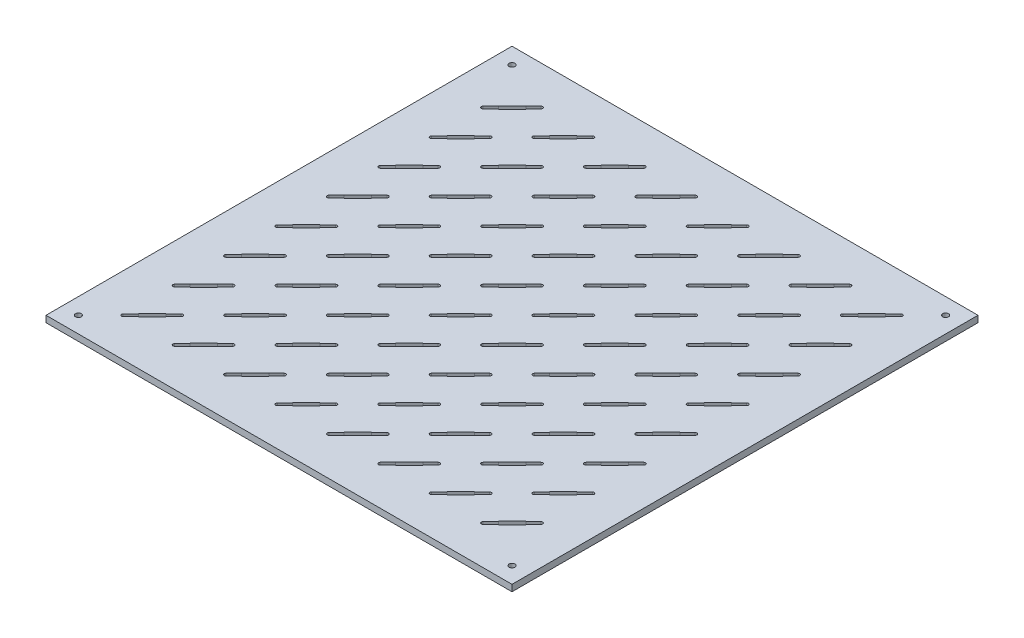
SolidWorks part; units mm, degrees
material "Acrylic (Medium-high impact)"
ref_plane "Front Plane" through (0, 0, 0) normal (0, 0, 1) x (1, 0, 0)
ref_plane "Top Plane" through (0, 0, 0) normal (0, 1, 0) x (1, 0, 0)
ref_plane "Right Plane" through (0, 0, 0) normal (1, 0, 0) x (0, 0, -1)
sketch "Sketch1" plane through (0, 0, 0) normal (0, 1, 0) x (1, 0, 0)
  line L1 (0, 0) -> (431.8, 0)
  line L2 (0, 0) -> (0, 431.8)
  line L3 (0, 431.8) -> (431.8, 431.8)
  line L4 (431.8, 0) -> (431.8, 431.8)
  dimension "D1" = 431.8
  dimension "D2" = 431.8
extrude "Boss-Extrude1" add sketch "Sketch1" along normal blind 6
sketch "Sketch2" plane through (0, 6, 0) normal (0, 1, 0) x (1, 0, 0)
  line L0 (73.025, 25.4) -> (73.025, 73.025) construction
  line L1 (25.4, 25.4) -> (73.025, 25.4) construction
  line L2 (25.4, 25.4) -> (25.4, 73.025) construction
  line L3 (25.4, 73.025) -> (73.025, 73.025) construction
  line L4 (73.025, 25.4) -> (73.025, 73.025) construction
  line L5 (73.025, 25.4) -> (120.65, 25.4) construction
  line L6 (120.65, 25.4) -> (120.65, 73.025) construction
  line L7 (73.025, 73.025) -> (120.65, 73.025) construction
  line L8 (120.65, 25.4) -> (120.65, 73.025) construction
  line L9 (120.65, 25.4) -> (168.275, 25.4) construction
  line L10 (168.275, 25.4) -> (168.275, 73.025) construction
  line L11 (120.65, 73.025) -> (168.275, 73.025) construction
  line L12 (168.275, 25.4) -> (168.275, 73.025) construction
  line L13 (168.275, 25.4) -> (215.9, 25.4) construction
  line L14 (215.9, 25.4) -> (215.9, 73.025) construction
  line L15 (168.275, 73.025) -> (215.9, 73.025) construction
  line L16 (215.9, 25.4) -> (215.9, 73.025) construction
  line L17 (215.9, 25.4) -> (263.525, 25.4) construction
  line L18 (263.525, 25.4) -> (263.525, 73.025) construction
  line L19 (215.9, 73.025) -> (263.525, 73.025) construction
  line L20 (263.525, 25.4) -> (263.525, 73.025) construction
  line L21 (263.525, 25.4) -> (311.15, 25.4) construction
  line L22 (311.15, 25.4) -> (311.15, 73.025) construction
  line L23 (263.525, 73.025) -> (311.15, 73.025) construction
  line L24 (311.15, 25.4) -> (311.15, 73.025) construction
  line L25 (311.15, 25.4) -> (358.775, 25.4) construction
  line L26 (358.775, 25.4) -> (358.775, 73.025) construction
  line L27 (311.15, 73.025) -> (358.775, 73.025) construction
  line L28 (358.775, 25.4) -> (358.775, 73.025) construction
  line L29 (358.775, 25.4) -> (406.4, 25.4) construction
  line L30 (406.4, 25.4) -> (406.4, 73.025) construction
  line L31 (358.775, 73.025) -> (406.4, 73.025) construction
  line L32 (73.025, 73.025) -> (73.025, 120.65) construction
  line L33 (73.025, 73.025) -> (120.65, 73.025) construction
  line L34 (120.65, 73.025) -> (120.65, 120.65) construction
  line L35 (73.025, 120.65) -> (120.65, 120.65) construction
  line L36 (120.65, 73.025) -> (120.65, 120.65) construction
  line L37 (120.65, 73.025) -> (168.275, 73.025) construction
  line L38 (168.275, 73.025) -> (168.275, 120.65) construction
  line L39 (120.65, 120.65) -> (168.275, 120.65) construction
  line L40 (168.275, 73.025) -> (168.275, 120.65) construction
  line L41 (168.275, 73.025) -> (215.9, 73.025) construction
  line L42 (215.9, 73.025) -> (215.9, 120.65) construction
  line L43 (168.275, 120.65) -> (215.9, 120.65) construction
  line L44 (215.9, 73.025) -> (215.9, 120.65) construction
  line L45 (215.9, 73.025) -> (263.525, 73.025) construction
  line L46 (263.525, 73.025) -> (263.525, 120.65) construction
  line L47 (215.9, 120.65) -> (263.525, 120.65) construction
  line L48 (263.525, 73.025) -> (263.525, 120.65) construction
  line L49 (263.525, 73.025) -> (311.15, 73.025) construction
  line L50 (311.15, 73.025) -> (311.15, 120.65) construction
  line L51 (263.525, 120.65) -> (311.15, 120.65) construction
  line L52 (311.15, 73.025) -> (311.15, 120.65) construction
  line L53 (311.15, 73.025) -> (358.775, 73.025) construction
  line L54 (358.775, 73.025) -> (358.775, 120.65) construction
  line L55 (311.15, 120.65) -> (358.775, 120.65) construction
  line L56 (358.775, 73.025) -> (358.775, 120.65) construction
  line L57 (358.775, 73.025) -> (406.4, 73.025) construction
  line L58 (406.4, 73.025) -> (406.4, 120.65) construction
  line L59 (358.775, 120.65) -> (406.4, 120.65) construction
  line L60 (73.025, 120.65) -> (73.025, 168.275) construction
  line L61 (73.025, 120.65) -> (120.65, 120.65) construction
  line L62 (120.65, 120.65) -> (120.65, 168.275) construction
  line L63 (73.025, 168.275) -> (120.65, 168.275) construction
  line L64 (120.65, 120.65) -> (120.65, 168.275) construction
  line L65 (120.65, 120.65) -> (168.275, 120.65) construction
  line L66 (168.275, 120.65) -> (168.275, 168.275) construction
  line L67 (120.65, 168.275) -> (168.275, 168.275) construction
  line L68 (168.275, 120.65) -> (168.275, 168.275) construction
  line L69 (168.275, 120.65) -> (215.9, 120.65) construction
  line L70 (215.9, 120.65) -> (215.9, 168.275) construction
  line L71 (168.275, 168.275) -> (215.9, 168.275) construction
  line L72 (215.9, 120.65) -> (215.9, 168.275) construction
  line L73 (215.9, 120.65) -> (263.525, 120.65) construction
  line L74 (263.525, 120.65) -> (263.525, 168.275) construction
  line L75 (215.9, 168.275) -> (263.525, 168.275) construction
  line L76 (263.525, 120.65) -> (263.525, 168.275) construction
  line L77 (263.525, 120.65) -> (311.15, 120.65) construction
  line L78 (311.15, 120.65) -> (311.15, 168.275) construction
  line L79 (263.525, 168.275) -> (311.15, 168.275) construction
  line L80 (311.15, 120.65) -> (311.15, 168.275) construction
  line L81 (311.15, 120.65) -> (358.775, 120.65) construction
  line L82 (358.775, 120.65) -> (358.775, 168.275) construction
  line L83 (311.15, 168.275) -> (358.775, 168.275) construction
  line L84 (358.775, 120.65) -> (358.775, 168.275) construction
  line L85 (358.775, 120.65) -> (406.4, 120.65) construction
  line L86 (406.4, 120.65) -> (406.4, 168.275) construction
  line L87 (358.775, 168.275) -> (406.4, 168.275) construction
  line L88 (73.025, 168.275) -> (73.025, 215.9) construction
  line L89 (73.025, 168.275) -> (120.65, 168.275) construction
  line L90 (120.65, 168.275) -> (120.65, 215.9) construction
  line L91 (73.025, 215.9) -> (120.65, 215.9) construction
  line L92 (120.65, 168.275) -> (120.65, 215.9) construction
  line L93 (120.65, 168.275) -> (168.275, 168.275) construction
  line L94 (168.275, 168.275) -> (168.275, 215.9) construction
  line L95 (120.65, 215.9) -> (168.275, 215.9) construction
  line L96 (168.275, 168.275) -> (168.275, 215.9) construction
  line L97 (168.275, 168.275) -> (215.9, 168.275) construction
  line L98 (215.9, 168.275) -> (215.9, 215.9) construction
  line L99 (168.275, 215.9) -> (215.9, 215.9) construction
  line L100 (215.9, 168.275) -> (215.9, 215.9) construction
  line L101 (215.9, 168.275) -> (263.525, 168.275) construction
  line L102 (263.525, 168.275) -> (263.525, 215.9) construction
  line L103 (215.9, 215.9) -> (263.525, 215.9) construction
  line L104 (263.525, 168.275) -> (263.525, 215.9) construction
  line L105 (263.525, 168.275) -> (311.15, 168.275) construction
  line L106 (311.15, 168.275) -> (311.15, 215.9) construction
  line L107 (263.525, 215.9) -> (311.15, 215.9) construction
  line L108 (311.15, 168.275) -> (311.15, 215.9) construction
  line L109 (311.15, 168.275) -> (358.775, 168.275) construction
  line L110 (358.775, 168.275) -> (358.775, 215.9) construction
  line L111 (311.15, 215.9) -> (358.775, 215.9) construction
  line L112 (358.775, 168.275) -> (358.775, 215.9) construction
  line L113 (358.775, 168.275) -> (406.4, 168.275) construction
  line L114 (406.4, 168.275) -> (406.4, 215.9) construction
  line L115 (358.775, 215.9) -> (406.4, 215.9) construction
  line L116 (73.025, 215.9) -> (73.025, 263.525) construction
  line L117 (73.025, 215.9) -> (120.65, 215.9) construction
  line L118 (120.65, 215.9) -> (120.65, 263.525) construction
  line L119 (73.025, 263.525) -> (120.65, 263.525) construction
  line L120 (120.65, 215.9) -> (120.65, 263.525) construction
  line L121 (120.65, 215.9) -> (168.275, 215.9) construction
  line L122 (168.275, 215.9) -> (168.275, 263.525) construction
  line L123 (120.65, 263.525) -> (168.275, 263.525) construction
  line L124 (168.275, 215.9) -> (168.275, 263.525) construction
  line L125 (168.275, 215.9) -> (215.9, 215.9) construction
  line L126 (215.9, 215.9) -> (215.9, 263.525) construction
  line L127 (168.275, 263.525) -> (215.9, 263.525) construction
  line L128 (215.9, 215.9) -> (215.9, 263.525) construction
  line L129 (215.9, 215.9) -> (263.525, 215.9) construction
  line L130 (263.525, 215.9) -> (263.525, 263.525) construction
  line L131 (215.9, 263.525) -> (263.525, 263.525) construction
  line L132 (263.525, 215.9) -> (263.525, 263.525) construction
  line L133 (263.525, 215.9) -> (311.15, 215.9) construction
  line L134 (311.15, 215.9) -> (311.15, 263.525) construction
  line L135 (263.525, 263.525) -> (311.15, 263.525) construction
  line L136 (311.15, 215.9) -> (311.15, 263.525) construction
  line L137 (311.15, 215.9) -> (358.775, 215.9) construction
  line L138 (358.775, 215.9) -> (358.775, 263.525) construction
  line L139 (311.15, 263.525) -> (358.775, 263.525) construction
  line L140 (358.775, 215.9) -> (358.775, 263.525) construction
  line L141 (358.775, 215.9) -> (406.4, 215.9) construction
  line L142 (406.4, 215.9) -> (406.4, 263.525) construction
  line L143 (358.775, 263.525) -> (406.4, 263.525) construction
  line L144 (73.025, 263.525) -> (73.025, 311.15) construction
  line L145 (73.025, 263.525) -> (120.65, 263.525) construction
  line L146 (120.65, 263.525) -> (120.65, 311.15) construction
  line L147 (73.025, 311.15) -> (120.65, 311.15) construction
  line L148 (120.65, 263.525) -> (120.65, 311.15) construction
  line L149 (120.65, 263.525) -> (168.275, 263.525) construction
  line L150 (168.275, 263.525) -> (168.275, 311.15) construction
  line L151 (120.65, 311.15) -> (168.275, 311.15) construction
  line L152 (168.275, 263.525) -> (168.275, 311.15) construction
  line L153 (168.275, 263.525) -> (215.9, 263.525) construction
  line L154 (215.9, 263.525) -> (215.9, 311.15) construction
  line L155 (168.275, 311.15) -> (215.9, 311.15) construction
  line L156 (215.9, 263.525) -> (215.9, 311.15) construction
  line L157 (215.9, 263.525) -> (263.525, 263.525) construction
  line L158 (263.525, 263.525) -> (263.525, 311.15) construction
  line L159 (215.9, 311.15) -> (263.525, 311.15) construction
  line L160 (263.525, 263.525) -> (263.525, 311.15) construction
  line L161 (263.525, 263.525) -> (311.15, 263.525) construction
  line L162 (311.15, 263.525) -> (311.15, 311.15) construction
  line L163 (263.525, 311.15) -> (311.15, 311.15) construction
  line L164 (311.15, 263.525) -> (311.15, 311.15) construction
  line L165 (311.15, 263.525) -> (358.775, 263.525) construction
  line L166 (358.775, 263.525) -> (358.775, 311.15) construction
  line L167 (311.15, 311.15) -> (358.775, 311.15) construction
  line L168 (358.775, 263.525) -> (358.775, 311.15) construction
  line L169 (358.775, 263.525) -> (406.4, 263.525) construction
  line L170 (406.4, 263.525) -> (406.4, 311.15) construction
  line L171 (358.775, 311.15) -> (406.4, 311.15) construction
  line L172 (73.025, 311.15) -> (73.025, 358.775) construction
  line L173 (73.025, 311.15) -> (120.65, 311.15) construction
  line L174 (120.65, 311.15) -> (120.65, 358.775) construction
  line L175 (73.025, 358.775) -> (120.65, 358.775) construction
  line L176 (120.65, 311.15) -> (120.65, 358.775) construction
  line L177 (120.65, 311.15) -> (168.275, 311.15) construction
  line L178 (168.275, 311.15) -> (168.275, 358.775) construction
  line L179 (120.65, 358.775) -> (168.275, 358.775) construction
  line L180 (168.275, 311.15) -> (168.275, 358.775) construction
  line L181 (168.275, 311.15) -> (215.9, 311.15) construction
  line L182 (215.9, 311.15) -> (215.9, 358.775) construction
  line L183 (168.275, 358.775) -> (215.9, 358.775) construction
  line L184 (215.9, 311.15) -> (215.9, 358.775) construction
  line L185 (215.9, 311.15) -> (263.525, 311.15) construction
  line L186 (263.525, 311.15) -> (263.525, 358.775) construction
  line L187 (215.9, 358.775) -> (263.525, 358.775) construction
  line L188 (263.525, 311.15) -> (263.525, 358.775) construction
  line L189 (263.525, 311.15) -> (311.15, 311.15) construction
  line L190 (311.15, 311.15) -> (311.15, 358.775) construction
  line L191 (263.525, 358.775) -> (311.15, 358.775) construction
  line L192 (311.15, 311.15) -> (311.15, 358.775) construction
  line L193 (311.15, 311.15) -> (358.775, 311.15) construction
  line L194 (358.775, 311.15) -> (358.775, 358.775) construction
  line L195 (311.15, 358.775) -> (358.775, 358.775) construction
  line L196 (358.775, 311.15) -> (358.775, 358.775) construction
  line L197 (358.775, 311.15) -> (406.4, 311.15) construction
  line L198 (406.4, 311.15) -> (406.4, 358.775) construction
  line L199 (358.775, 358.775) -> (406.4, 358.775) construction
  line L200 (73.025, 358.775) -> (73.025, 406.4) construction
  line L201 (73.025, 358.775) -> (120.65, 358.775) construction
  line L202 (120.65, 358.775) -> (120.65, 406.4) construction
  line L203 (73.025, 406.4) -> (120.65, 406.4) construction
  line L204 (120.65, 358.775) -> (120.65, 406.4) construction
  line L205 (120.65, 358.775) -> (168.275, 358.775) construction
  line L206 (168.275, 358.775) -> (168.275, 406.4) construction
  line L207 (120.65, 406.4) -> (168.275, 406.4) construction
  line L208 (168.275, 358.775) -> (168.275, 406.4) construction
  line L209 (168.275, 358.775) -> (215.9, 358.775) construction
  line L210 (215.9, 358.775) -> (215.9, 406.4) construction
  line L211 (168.275, 406.4) -> (215.9, 406.4) construction
  line L212 (215.9, 358.775) -> (215.9, 406.4) construction
  line L213 (215.9, 358.775) -> (263.525, 358.775) construction
  line L214 (263.525, 358.775) -> (263.525, 406.4) construction
  line L215 (215.9, 406.4) -> (263.525, 406.4) construction
  line L216 (263.525, 358.775) -> (263.525, 406.4) construction
  line L217 (263.525, 358.775) -> (311.15, 358.775) construction
  line L218 (311.15, 358.775) -> (311.15, 406.4) construction
  line L219 (263.525, 406.4) -> (311.15, 406.4) construction
  line L220 (311.15, 358.775) -> (311.15, 406.4) construction
  line L221 (311.15, 358.775) -> (358.775, 358.775) construction
  line L222 (358.775, 358.775) -> (358.775, 406.4) construction
  line L223 (311.15, 406.4) -> (358.775, 406.4) construction
  line L224 (358.775, 358.775) -> (358.775, 406.4) construction
  line L225 (358.775, 358.775) -> (406.4, 358.775) construction
  line L226 (406.4, 358.775) -> (406.4, 406.4) construction
  line L227 (358.775, 406.4) -> (406.4, 406.4) construction
  line L228 (25.4, 73.025) -> (25.4, 120.65) construction
  line L229 (25.4, 73.025) -> (73.025, 73.025) construction
  line L230 (73.025, 73.025) -> (73.025, 120.65) construction
  line L231 (25.4, 120.65) -> (73.025, 120.65) construction
  line L232 (25.4, 120.65) -> (25.4, 168.275) construction
  line L233 (25.4, 120.65) -> (73.025, 120.65) construction
  line L234 (73.025, 120.65) -> (73.025, 168.275) construction
  line L235 (25.4, 168.275) -> (73.025, 168.275) construction
  line L236 (25.4, 168.275) -> (25.4, 215.9) construction
  line L237 (25.4, 168.275) -> (73.025, 168.275) construction
  line L238 (73.025, 168.275) -> (73.025, 215.9) construction
  line L239 (25.4, 215.9) -> (73.025, 215.9) construction
  line L240 (25.4, 215.9) -> (25.4, 263.525) construction
  line L241 (25.4, 215.9) -> (73.025, 215.9) construction
  line L242 (73.025, 215.9) -> (73.025, 263.525) construction
  line L243 (25.4, 263.525) -> (73.025, 263.525) construction
  line L244 (25.4, 263.525) -> (25.4, 311.15) construction
  line L245 (25.4, 263.525) -> (73.025, 263.525) construction
  line L246 (73.025, 263.525) -> (73.025, 311.15) construction
  line L247 (25.4, 311.15) -> (73.025, 311.15) construction
  line L248 (25.4, 311.15) -> (25.4, 358.775) construction
  line L249 (25.4, 311.15) -> (73.025, 311.15) construction
  line L250 (73.025, 311.15) -> (73.025, 358.775) construction
  line L251 (25.4, 358.775) -> (73.025, 358.775) construction
  line L252 (25.4, 358.775) -> (25.4, 406.4) construction
  line L253 (25.4, 358.775) -> (73.025, 358.775) construction
  line L254 (73.025, 358.775) -> (73.025, 406.4) construction
  line L255 (25.4, 406.4) -> (73.025, 406.4) construction
  line L256 (0, 0) -> (431.8, 0) construction
  line L257 (0, 431.8) -> (0, 0) construction
  line L259 (431.8, 431.8) -> (0, 431.8) construction
  line L260 (431.8, 0) -> (431.8, 431.8) construction
  line L261 (73.025, 73.025) -> (25.4, 25.4) construction
  line L266 (41.7253, 43.9704) -> (34.6543, 36.8993)
  line L906 (56.99, 54.1616) -> (56.6983, 54.4532)
  line L922 (56.99, 54.1616) -> (44.2621, 41.4336)
  line L923 (44.2621, 41.4336) -> (43.9704, 41.7253)
  line L924 (54.1616, 56.99) -> (41.4336, 44.2621)
  line L925 (34.6543, 36.8993) -> (36.8993, 34.6543)
  line L926 (36.8993, 34.6543) -> (43.9704, 41.7253)
  line L927 (41.7253, 43.9704) -> (41.4336, 44.2621)
  line L928 (54.4532, 56.6983) -> (61.5243, 63.7694)
  line L929 (61.5243, 63.7694) -> (63.7694, 61.5243)
  line L930 (63.7694, 61.5243) -> (56.6983, 54.4532)
  line L931 (54.4532, 56.6983) -> (54.1616, 56.99)
  line L932 (25.4, 73.025) -> (73.025, 25.4) construction
  line L933 (56.99, 101.7916) -> (56.6983, 102.0832)
  line L934 (63.7694, 109.1543) -> (56.6983, 102.0832)
  line L935 (61.5243, 111.3994) -> (63.7694, 109.1543)
  line L936 (54.4532, 104.3283) -> (61.5243, 111.3994)
  line L937 (54.4532, 104.3283) -> (54.1616, 104.62)
  line L938 (54.1616, 104.62) -> (41.4336, 91.8921)
  line L939 (41.7253, 91.6004) -> (41.4336, 91.8921)
  line L940 (41.7253, 91.6004) -> (34.6543, 84.5293)
  line L941 (34.6543, 84.5293) -> (36.8993, 82.2843)
  line L942 (36.8993, 82.2843) -> (43.9704, 89.3553)
  line L943 (44.2621, 89.0636) -> (43.9704, 89.3553)
  line L944 (56.99, 101.7916) -> (44.2621, 89.0636)
  line L945 (56.99, 149.4216) -> (56.6983, 149.7132)
  line L946 (63.7694, 156.7843) -> (56.6983, 149.7132)
  line L947 (61.5243, 159.0294) -> (63.7694, 156.7843)
  line L948 (54.4532, 151.9583) -> (61.5243, 159.0294)
  line L949 (54.4532, 151.9583) -> (54.1616, 152.25)
  line L950 (54.1616, 152.25) -> (41.4336, 139.5221)
  line L951 (41.7253, 139.2304) -> (41.4336, 139.5221)
  line L952 (41.7253, 139.2304) -> (34.6543, 132.1593)
  line L953 (34.6543, 132.1593) -> (36.8993, 129.9143)
  line L954 (36.8993, 129.9143) -> (43.9704, 136.9853)
  line L955 (44.2621, 136.6936) -> (43.9704, 136.9853)
  line L956 (56.99, 149.4216) -> (44.2621, 136.6936)
  line L957 (56.99, 197.0516) -> (56.6983, 197.3432)
  line L958 (63.7694, 204.4143) -> (56.6983, 197.3432)
  line L959 (61.5243, 206.6594) -> (63.7694, 204.4143)
  line L960 (54.4532, 199.5883) -> (61.5243, 206.6594)
  line L961 (54.4532, 199.5883) -> (54.1616, 199.88)
  line L962 (54.1616, 199.88) -> (41.4336, 187.1521)
  line L963 (41.7253, 186.8604) -> (41.4336, 187.1521)
  line L964 (41.7253, 186.8604) -> (34.6543, 179.7893)
  line L965 (34.6543, 179.7893) -> (36.8993, 177.5443)
  line L966 (36.8993, 177.5443) -> (43.9704, 184.6153)
  line L967 (44.2621, 184.3236) -> (43.9704, 184.6153)
  line L968 (56.99, 197.0516) -> (44.2621, 184.3236)
  line L969 (56.99, 244.6816) -> (56.6983, 244.9732)
  line L970 (63.7694, 252.0443) -> (56.6983, 244.9732)
  line L971 (61.5243, 254.2894) -> (63.7694, 252.0443)
  line L972 (54.4532, 247.2183) -> (61.5243, 254.2894)
  line L973 (54.4532, 247.2183) -> (54.1616, 247.51)
  line L974 (54.1616, 247.51) -> (41.4336, 234.7821)
  line L975 (41.7253, 234.4904) -> (41.4336, 234.7821)
  line L976 (41.7253, 234.4904) -> (34.6543, 227.4193)
  line L977 (34.6543, 227.4193) -> (36.8993, 225.1743)
  line L978 (36.8993, 225.1743) -> (43.9704, 232.2453)
  line L979 (44.2621, 231.9536) -> (43.9704, 232.2453)
  line L980 (56.99, 244.6816) -> (44.2621, 231.9536)
  line L981 (56.99, 292.3116) -> (56.6983, 292.6032)
  line L982 (63.7694, 299.6743) -> (56.6983, 292.6032)
  line L983 (61.5243, 301.9194) -> (63.7694, 299.6743)
  line L984 (54.4532, 294.8483) -> (61.5243, 301.9194)
  line L985 (54.4532, 294.8483) -> (54.1616, 295.14)
  line L986 (54.1616, 295.14) -> (41.4336, 282.4121)
  line L987 (41.7253, 282.1204) -> (41.4336, 282.4121)
  line L988 (41.7253, 282.1204) -> (34.6543, 275.0493)
  line L989 (34.6543, 275.0493) -> (36.8993, 272.8043)
  line L990 (36.8993, 272.8043) -> (43.9704, 279.8753)
  line L991 (44.2621, 279.5836) -> (43.9704, 279.8753)
  line L992 (56.99, 292.3116) -> (44.2621, 279.5836)
  line L993 (56.99, 339.9416) -> (56.6983, 340.2332)
  line L994 (63.7694, 347.3043) -> (56.6983, 340.2332)
  line L995 (61.5243, 349.5494) -> (63.7694, 347.3043)
  line L996 (54.4532, 342.4783) -> (61.5243, 349.5494)
  line L997 (54.4532, 342.4783) -> (54.1616, 342.77)
  line L998 (54.1616, 342.77) -> (41.4336, 330.0421)
  line L999 (41.7253, 329.7504) -> (41.4336, 330.0421)
  line L1000 (41.7253, 329.7504) -> (34.6543, 322.6793)
  line L1001 (34.6543, 322.6793) -> (36.8993, 320.4343)
  line L1002 (36.8993, 320.4343) -> (43.9704, 327.5053)
  line L1003 (44.2621, 327.2136) -> (43.9704, 327.5053)
  line L1004 (56.99, 339.9416) -> (44.2621, 327.2136)
  line L1005 (56.99, 387.5716) -> (56.6983, 387.8632)
  line L1006 (63.7694, 394.9343) -> (56.6983, 387.8632)
  line L1007 (61.5243, 397.1794) -> (63.7694, 394.9343)
  line L1008 (54.4532, 390.1083) -> (61.5243, 397.1794)
  line L1009 (54.4532, 390.1083) -> (54.1616, 390.4)
  line L1010 (54.1616, 390.4) -> (41.4336, 377.6721)
  line L1011 (41.7253, 377.3804) -> (41.4336, 377.6721)
  line L1012 (41.7253, 377.3804) -> (34.6543, 370.3093)
  line L1013 (34.6543, 370.3093) -> (36.8993, 368.0643)
  line L1014 (36.8993, 368.0643) -> (43.9704, 375.1353)
  line L1015 (44.2621, 374.8436) -> (43.9704, 375.1353)
  line L1016 (56.99, 387.5716) -> (44.2621, 374.8436)
  line L1017 (104.62, 101.7916) -> (104.3283, 102.0832)
  line L1018 (111.3994, 109.1543) -> (104.3283, 102.0832)
  line L1019 (109.1543, 111.3994) -> (111.3994, 109.1543)
  line L1020 (102.0832, 104.3283) -> (109.1543, 111.3994)
  line L1021 (102.0832, 104.3283) -> (101.7916, 104.62)
  line L1022 (101.7916, 104.62) -> (89.0636, 91.8921)
  line L1023 (89.3553, 91.6004) -> (89.0636, 91.8921)
  line L1024 (89.3553, 91.6004) -> (82.2843, 84.5293)
  line L1025 (82.2843, 84.5293) -> (84.5293, 82.2843)
  line L1026 (84.5293, 82.2843) -> (91.6004, 89.3553)
  line L1027 (91.8921, 89.0636) -> (91.6004, 89.3553)
  line L1028 (104.62, 101.7916) -> (91.8921, 89.0636)
  line L1029 (104.62, 149.4216) -> (104.3283, 149.7132)
  line L1030 (111.3994, 156.7843) -> (104.3283, 149.7132)
  line L1031 (109.1543, 159.0294) -> (111.3994, 156.7843)
  line L1032 (102.0832, 151.9583) -> (109.1543, 159.0294)
  line L1033 (102.0832, 151.9583) -> (101.7916, 152.25)
  line L1034 (101.7916, 152.25) -> (89.0636, 139.5221)
  line L1035 (89.3553, 139.2304) -> (89.0636, 139.5221)
  line L1036 (89.3553, 139.2304) -> (82.2843, 132.1593)
  line L1037 (82.2843, 132.1593) -> (84.5293, 129.9143)
  line L1038 (84.5293, 129.9143) -> (91.6004, 136.9853)
  line L1039 (91.8921, 136.6936) -> (91.6004, 136.9853)
  line L1040 (104.62, 149.4216) -> (91.8921, 136.6936)
  line L1041 (104.62, 197.0516) -> (104.3283, 197.3432)
  line L1042 (111.3994, 204.4143) -> (104.3283, 197.3432)
  line L1043 (109.1543, 206.6594) -> (111.3994, 204.4143)
  line L1044 (102.0832, 199.5883) -> (109.1543, 206.6594)
  line L1045 (102.0832, 199.5883) -> (101.7916, 199.88)
  line L1046 (101.7916, 199.88) -> (89.0636, 187.1521)
  line L1047 (89.3553, 186.8604) -> (89.0636, 187.1521)
  line L1048 (89.3553, 186.8604) -> (82.2843, 179.7893)
  line L1049 (82.2843, 179.7893) -> (84.5293, 177.5443)
  line L1050 (84.5293, 177.5443) -> (91.6004, 184.6153)
  line L1051 (91.8921, 184.3236) -> (91.6004, 184.6153)
  line L1052 (104.62, 197.0516) -> (91.8921, 184.3236)
  line L1053 (104.62, 244.6816) -> (104.3283, 244.9732)
  line L1054 (111.3994, 252.0443) -> (104.3283, 244.9732)
  line L1055 (109.1543, 254.2894) -> (111.3994, 252.0443)
  line L1056 (102.0832, 247.2183) -> (109.1543, 254.2894)
  line L1057 (102.0832, 247.2183) -> (101.7916, 247.51)
  line L1058 (101.7916, 247.51) -> (89.0636, 234.7821)
  line L1059 (89.3553, 234.4904) -> (89.0636, 234.7821)
  line L1060 (89.3553, 234.4904) -> (82.2843, 227.4193)
  line L1061 (82.2843, 227.4193) -> (84.5293, 225.1743)
  line L1062 (84.5293, 225.1743) -> (91.6004, 232.2453)
  line L1063 (91.8921, 231.9536) -> (91.6004, 232.2453)
  line L1064 (104.62, 244.6816) -> (91.8921, 231.9536)
  line L1065 (104.62, 292.3116) -> (104.3283, 292.6032)
  line L1066 (111.3994, 299.6743) -> (104.3283, 292.6032)
  line L1067 (109.1543, 301.9194) -> (111.3994, 299.6743)
  line L1068 (102.0832, 294.8483) -> (109.1543, 301.9194)
  line L1069 (102.0832, 294.8483) -> (101.7916, 295.14)
  line L1070 (101.7916, 295.14) -> (89.0636, 282.4121)
  line L1071 (89.3553, 282.1204) -> (89.0636, 282.4121)
  line L1072 (89.3553, 282.1204) -> (82.2843, 275.0493)
  line L1073 (82.2843, 275.0493) -> (84.5293, 272.8043)
  line L1074 (84.5293, 272.8043) -> (91.6004, 279.8753)
  line L1075 (91.8921, 279.5836) -> (91.6004, 279.8753)
  line L1076 (104.62, 292.3116) -> (91.8921, 279.5836)
  line L1077 (104.62, 339.9416) -> (104.3283, 340.2332)
  line L1078 (111.3994, 347.3043) -> (104.3283, 340.2332)
  line L1079 (109.1543, 349.5494) -> (111.3994, 347.3043)
  line L1080 (102.0832, 342.4783) -> (109.1543, 349.5494)
  line L1081 (102.0832, 342.4783) -> (101.7916, 342.77)
  line L1082 (101.7916, 342.77) -> (89.0636, 330.0421)
  line L1083 (89.3553, 329.7504) -> (89.0636, 330.0421)
  line L1084 (89.3553, 329.7504) -> (82.2843, 322.6793)
  line L1085 (82.2843, 322.6793) -> (84.5293, 320.4343)
  line L1086 (84.5293, 320.4343) -> (91.6004, 327.5053)
  line L1087 (91.8921, 327.2136) -> (91.6004, 327.5053)
  line L1088 (104.62, 339.9416) -> (91.8921, 327.2136)
  line L1089 (104.62, 387.5716) -> (104.3283, 387.8632)
  line L1090 (111.3994, 394.9343) -> (104.3283, 387.8632)
  line L1091 (109.1543, 397.1794) -> (111.3994, 394.9343)
  line L1092 (102.0832, 390.1083) -> (109.1543, 397.1794)
  line L1093 (102.0832, 390.1083) -> (101.7916, 390.4)
  line L1094 (101.7916, 390.4) -> (89.0636, 377.6721)
  line L1095 (89.3553, 377.3804) -> (89.0636, 377.6721)
  line L1096 (89.3553, 377.3804) -> (82.2843, 370.3093)
  line L1097 (82.2843, 370.3093) -> (84.5293, 368.0643)
  line L1098 (84.5293, 368.0643) -> (91.6004, 375.1353)
  line L1099 (91.8921, 374.8436) -> (91.6004, 375.1353)
  line L1100 (104.62, 387.5716) -> (91.8921, 374.8436)
  line L1101 (152.25, 101.7916) -> (151.9583, 102.0832)
  line L1102 (159.0294, 109.1543) -> (151.9583, 102.0832)
  line L1103 (156.7843, 111.3994) -> (159.0294, 109.1543)
  line L1104 (149.7132, 104.3283) -> (156.7843, 111.3994)
  line L1105 (149.7132, 104.3283) -> (149.4216, 104.62)
  line L1106 (149.4216, 104.62) -> (136.6936, 91.8921)
  line L1107 (136.9853, 91.6004) -> (136.6936, 91.8921)
  line L1108 (136.9853, 91.6004) -> (129.9143, 84.5293)
  line L1109 (129.9143, 84.5293) -> (132.1593, 82.2843)
  line L1110 (132.1593, 82.2843) -> (139.2304, 89.3553)
  line L1111 (139.5221, 89.0636) -> (139.2304, 89.3553)
  line L1112 (152.25, 101.7916) -> (139.5221, 89.0636)
  line L1113 (152.25, 149.4216) -> (151.9583, 149.7132)
  line L1114 (159.0294, 156.7843) -> (151.9583, 149.7132)
  line L1115 (156.7843, 159.0294) -> (159.0294, 156.7843)
  line L1116 (149.7132, 151.9583) -> (156.7843, 159.0294)
  line L1117 (149.7132, 151.9583) -> (149.4216, 152.25)
  line L1118 (149.4216, 152.25) -> (136.6936, 139.5221)
  line L1119 (136.9853, 139.2304) -> (136.6936, 139.5221)
  line L1120 (136.9853, 139.2304) -> (129.9143, 132.1593)
  line L1121 (129.9143, 132.1593) -> (132.1593, 129.9143)
  line L1122 (132.1593, 129.9143) -> (139.2304, 136.9853)
  line L1123 (139.5221, 136.6936) -> (139.2304, 136.9853)
  line L1124 (152.25, 149.4216) -> (139.5221, 136.6936)
  line L1125 (152.25, 197.0516) -> (151.9583, 197.3432)
  line L1126 (159.0294, 204.4143) -> (151.9583, 197.3432)
  line L1127 (156.7843, 206.6594) -> (159.0294, 204.4143)
  line L1128 (149.7132, 199.5883) -> (156.7843, 206.6594)
  line L1129 (149.7132, 199.5883) -> (149.4216, 199.88)
  line L1130 (149.4216, 199.88) -> (136.6936, 187.1521)
  line L1131 (136.9853, 186.8604) -> (136.6936, 187.1521)
  line L1132 (136.9853, 186.8604) -> (129.9143, 179.7893)
  line L1133 (129.9143, 179.7893) -> (132.1593, 177.5443)
  line L1134 (132.1593, 177.5443) -> (139.2304, 184.6153)
  line L1135 (139.5221, 184.3236) -> (139.2304, 184.6153)
  line L1136 (152.25, 197.0516) -> (139.5221, 184.3236)
  line L1137 (152.25, 244.6816) -> (151.9583, 244.9732)
  line L1138 (159.0294, 252.0443) -> (151.9583, 244.9732)
  line L1139 (156.7843, 254.2894) -> (159.0294, 252.0443)
  line L1140 (149.7132, 247.2183) -> (156.7843, 254.2894)
  line L1141 (149.7132, 247.2183) -> (149.4216, 247.51)
  line L1142 (149.4216, 247.51) -> (136.6936, 234.7821)
  line L1143 (136.9853, 234.4904) -> (136.6936, 234.7821)
  line L1144 (136.9853, 234.4904) -> (129.9143, 227.4193)
  line L1145 (129.9143, 227.4193) -> (132.1593, 225.1743)
  line L1146 (132.1593, 225.1743) -> (139.2304, 232.2453)
  line L1147 (139.5221, 231.9536) -> (139.2304, 232.2453)
  line L1148 (152.25, 244.6816) -> (139.5221, 231.9536)
  line L1149 (152.25, 292.3116) -> (151.9583, 292.6032)
  line L1150 (159.0294, 299.6743) -> (151.9583, 292.6032)
  line L1151 (156.7843, 301.9194) -> (159.0294, 299.6743)
  line L1152 (149.7132, 294.8483) -> (156.7843, 301.9194)
  line L1153 (149.7132, 294.8483) -> (149.4216, 295.14)
  line L1154 (149.4216, 295.14) -> (136.6936, 282.4121)
  line L1155 (136.9853, 282.1204) -> (136.6936, 282.4121)
  line L1156 (136.9853, 282.1204) -> (129.9143, 275.0493)
  line L1157 (129.9143, 275.0493) -> (132.1593, 272.8043)
  line L1158 (132.1593, 272.8043) -> (139.2304, 279.8753)
  line L1159 (139.5221, 279.5836) -> (139.2304, 279.8753)
  line L1160 (152.25, 292.3116) -> (139.5221, 279.5836)
  line L1161 (152.25, 339.9416) -> (151.9583, 340.2332)
  line L1162 (159.0294, 347.3043) -> (151.9583, 340.2332)
  line L1163 (156.7843, 349.5494) -> (159.0294, 347.3043)
  line L1164 (149.7132, 342.4783) -> (156.7843, 349.5494)
  line L1165 (149.7132, 342.4783) -> (149.4216, 342.77)
  line L1166 (149.4216, 342.77) -> (136.6936, 330.0421)
  line L1167 (136.9853, 329.7504) -> (136.6936, 330.0421)
  line L1168 (136.9853, 329.7504) -> (129.9143, 322.6793)
  line L1169 (129.9143, 322.6793) -> (132.1593, 320.4343)
  line L1170 (132.1593, 320.4343) -> (139.2304, 327.5053)
  line L1171 (139.5221, 327.2136) -> (139.2304, 327.5053)
  line L1172 (152.25, 339.9416) -> (139.5221, 327.2136)
  line L1173 (152.25, 387.5716) -> (151.9583, 387.8632)
  line L1174 (159.0294, 394.9343) -> (151.9583, 387.8632)
  line L1175 (156.7843, 397.1794) -> (159.0294, 394.9343)
  line L1176 (149.7132, 390.1083) -> (156.7843, 397.1794)
  line L1177 (149.7132, 390.1083) -> (149.4216, 390.4)
  line L1178 (149.4216, 390.4) -> (136.6936, 377.6721)
  line L1179 (136.9853, 377.3804) -> (136.6936, 377.6721)
  line L1180 (136.9853, 377.3804) -> (129.9143, 370.3093)
  line L1181 (129.9143, 370.3093) -> (132.1593, 368.0643)
  line L1182 (132.1593, 368.0643) -> (139.2304, 375.1353)
  line L1183 (139.5221, 374.8436) -> (139.2304, 375.1353)
  line L1184 (152.25, 387.5716) -> (139.5221, 374.8436)
  line L1185 (199.88, 101.7916) -> (199.5883, 102.0832)
  line L1186 (206.6594, 109.1543) -> (199.5883, 102.0832)
  line L1187 (204.4143, 111.3994) -> (206.6594, 109.1543)
  line L1188 (197.3432, 104.3283) -> (204.4143, 111.3994)
  line L1189 (197.3432, 104.3283) -> (197.0516, 104.62)
  line L1190 (197.0516, 104.62) -> (184.3236, 91.8921)
  line L1191 (184.6153, 91.6004) -> (184.3236, 91.8921)
  line L1192 (184.6153, 91.6004) -> (177.5443, 84.5293)
  line L1193 (177.5443, 84.5293) -> (179.7893, 82.2843)
  line L1194 (179.7893, 82.2843) -> (186.8604, 89.3553)
  line L1195 (187.1521, 89.0636) -> (186.8604, 89.3553)
  line L1196 (199.88, 101.7916) -> (187.1521, 89.0636)
  line L1197 (199.88, 149.4216) -> (199.5883, 149.7132)
  line L1198 (206.6594, 156.7843) -> (199.5883, 149.7132)
  line L1199 (204.4143, 159.0294) -> (206.6594, 156.7843)
  line L1200 (197.3432, 151.9583) -> (204.4143, 159.0294)
  line L1201 (197.3432, 151.9583) -> (197.0516, 152.25)
  line L1202 (197.0516, 152.25) -> (184.3236, 139.5221)
  line L1203 (184.6153, 139.2304) -> (184.3236, 139.5221)
  line L1204 (184.6153, 139.2304) -> (177.5443, 132.1593)
  line L1205 (177.5443, 132.1593) -> (179.7893, 129.9143)
  line L1206 (179.7893, 129.9143) -> (186.8604, 136.9853)
  line L1207 (187.1521, 136.6936) -> (186.8604, 136.9853)
  line L1208 (199.88, 149.4216) -> (187.1521, 136.6936)
  line L1209 (199.88, 197.0516) -> (199.5883, 197.3432)
  line L1210 (206.6594, 204.4143) -> (199.5883, 197.3432)
  line L1211 (204.4143, 206.6594) -> (206.6594, 204.4143)
  line L1212 (197.3432, 199.5883) -> (204.4143, 206.6594)
  line L1213 (197.3432, 199.5883) -> (197.0516, 199.88)
  line L1214 (197.0516, 199.88) -> (184.3236, 187.1521)
  line L1215 (184.6153, 186.8604) -> (184.3236, 187.1521)
  line L1216 (184.6153, 186.8604) -> (177.5443, 179.7893)
  line L1217 (177.5443, 179.7893) -> (179.7893, 177.5443)
  line L1218 (179.7893, 177.5443) -> (186.8604, 184.6153)
  line L1219 (187.1521, 184.3236) -> (186.8604, 184.6153)
  line L1220 (199.88, 197.0516) -> (187.1521, 184.3236)
  line L1221 (199.88, 244.6816) -> (199.5883, 244.9732)
  line L1222 (206.6594, 252.0443) -> (199.5883, 244.9732)
  line L1223 (204.4143, 254.2894) -> (206.6594, 252.0443)
  line L1224 (197.3432, 247.2183) -> (204.4143, 254.2894)
  line L1225 (197.3432, 247.2183) -> (197.0516, 247.51)
  line L1226 (197.0516, 247.51) -> (184.3236, 234.7821)
  line L1227 (184.6153, 234.4904) -> (184.3236, 234.7821)
  line L1228 (184.6153, 234.4904) -> (177.5443, 227.4193)
  line L1229 (177.5443, 227.4193) -> (179.7893, 225.1743)
  line L1230 (179.7893, 225.1743) -> (186.8604, 232.2453)
  line L1231 (187.1521, 231.9536) -> (186.8604, 232.2453)
  line L1232 (199.88, 244.6816) -> (187.1521, 231.9536)
  line L1233 (199.88, 292.3116) -> (199.5883, 292.6032)
  line L1234 (206.6594, 299.6743) -> (199.5883, 292.6032)
  line L1235 (204.4143, 301.9194) -> (206.6594, 299.6743)
  line L1236 (197.3432, 294.8483) -> (204.4143, 301.9194)
  line L1237 (197.3432, 294.8483) -> (197.0516, 295.14)
  line L1238 (197.0516, 295.14) -> (184.3236, 282.4121)
  line L1239 (184.6153, 282.1204) -> (184.3236, 282.4121)
  line L1240 (184.6153, 282.1204) -> (177.5443, 275.0493)
  line L1241 (177.5443, 275.0493) -> (179.7893, 272.8043)
  line L1242 (179.7893, 272.8043) -> (186.8604, 279.8753)
  line L1243 (187.1521, 279.5836) -> (186.8604, 279.8753)
  line L1244 (199.88, 292.3116) -> (187.1521, 279.5836)
  line L1245 (199.88, 339.9416) -> (199.5883, 340.2332)
  line L1246 (206.6594, 347.3043) -> (199.5883, 340.2332)
  line L1247 (204.4143, 349.5494) -> (206.6594, 347.3043)
  line L1248 (197.3432, 342.4783) -> (204.4143, 349.5494)
  line L1249 (197.3432, 342.4783) -> (197.0516, 342.77)
  line L1250 (197.0516, 342.77) -> (184.3236, 330.0421)
  line L1251 (184.6153, 329.7504) -> (184.3236, 330.0421)
  line L1252 (184.6153, 329.7504) -> (177.5443, 322.6793)
  line L1253 (177.5443, 322.6793) -> (179.7893, 320.4343)
  line L1254 (179.7893, 320.4343) -> (186.8604, 327.5053)
  line L1255 (187.1521, 327.2136) -> (186.8604, 327.5053)
  line L1256 (199.88, 339.9416) -> (187.1521, 327.2136)
  line L1257 (199.88, 387.5716) -> (199.5883, 387.8632)
  line L1258 (206.6594, 394.9343) -> (199.5883, 387.8632)
  line L1259 (204.4143, 397.1794) -> (206.6594, 394.9343)
  line L1260 (197.3432, 390.1083) -> (204.4143, 397.1794)
  line L1261 (197.3432, 390.1083) -> (197.0516, 390.4)
  line L1262 (197.0516, 390.4) -> (184.3236, 377.6721)
  line L1263 (184.6153, 377.3804) -> (184.3236, 377.6721)
  line L1264 (184.6153, 377.3804) -> (177.5443, 370.3093)
  line L1265 (177.5443, 370.3093) -> (179.7893, 368.0643)
  line L1266 (179.7893, 368.0643) -> (186.8604, 375.1353)
  line L1267 (187.1521, 374.8436) -> (186.8604, 375.1353)
  line L1268 (199.88, 387.5716) -> (187.1521, 374.8436)
  line L1269 (247.51, 101.7916) -> (247.2183, 102.0832)
  line L1270 (254.2894, 109.1543) -> (247.2183, 102.0832)
  line L1271 (252.0443, 111.3994) -> (254.2894, 109.1543)
  line L1272 (244.9732, 104.3283) -> (252.0443, 111.3994)
  line L1273 (244.9732, 104.3283) -> (244.6816, 104.62)
  line L1274 (244.6816, 104.62) -> (231.9536, 91.8921)
  line L1275 (232.2453, 91.6004) -> (231.9536, 91.8921)
  line L1276 (232.2453, 91.6004) -> (225.1743, 84.5293)
  line L1277 (225.1743, 84.5293) -> (227.4193, 82.2843)
  line L1278 (227.4193, 82.2843) -> (234.4904, 89.3553)
  line L1279 (234.7821, 89.0636) -> (234.4904, 89.3553)
  line L1280 (247.51, 101.7916) -> (234.7821, 89.0636)
  line L1281 (247.51, 149.4216) -> (247.2183, 149.7132)
  line L1282 (254.2894, 156.7843) -> (247.2183, 149.7132)
  line L1283 (252.0443, 159.0294) -> (254.2894, 156.7843)
  line L1284 (244.9732, 151.9583) -> (252.0443, 159.0294)
  line L1285 (244.9732, 151.9583) -> (244.6816, 152.25)
  line L1286 (244.6816, 152.25) -> (231.9536, 139.5221)
  line L1287 (232.2453, 139.2304) -> (231.9536, 139.5221)
  line L1288 (232.2453, 139.2304) -> (225.1743, 132.1593)
  line L1289 (225.1743, 132.1593) -> (227.4193, 129.9143)
  line L1290 (227.4193, 129.9143) -> (234.4904, 136.9853)
  line L1291 (234.7821, 136.6936) -> (234.4904, 136.9853)
  line L1292 (247.51, 149.4216) -> (234.7821, 136.6936)
  line L1293 (247.51, 197.0516) -> (247.2183, 197.3432)
  line L1294 (254.2894, 204.4143) -> (247.2183, 197.3432)
  line L1295 (252.0443, 206.6594) -> (254.2894, 204.4143)
  line L1296 (244.9732, 199.5883) -> (252.0443, 206.6594)
  line L1297 (244.9732, 199.5883) -> (244.6816, 199.88)
  line L1298 (244.6816, 199.88) -> (231.9536, 187.1521)
  line L1299 (232.2453, 186.8604) -> (231.9536, 187.1521)
  line L1300 (232.2453, 186.8604) -> (225.1743, 179.7893)
  line L1301 (225.1743, 179.7893) -> (227.4193, 177.5443)
  line L1302 (227.4193, 177.5443) -> (234.4904, 184.6153)
  line L1303 (234.7821, 184.3236) -> (234.4904, 184.6153)
  line L1304 (247.51, 197.0516) -> (234.7821, 184.3236)
  line L1305 (247.51, 244.6816) -> (247.2183, 244.9732)
  line L1306 (254.2894, 252.0443) -> (247.2183, 244.9732)
  line L1307 (252.0443, 254.2894) -> (254.2894, 252.0443)
  line L1308 (244.9732, 247.2183) -> (252.0443, 254.2894)
  line L1309 (244.9732, 247.2183) -> (244.6816, 247.51)
  line L1310 (244.6816, 247.51) -> (231.9536, 234.7821)
  line L1311 (232.2453, 234.4904) -> (231.9536, 234.7821)
  line L1312 (232.2453, 234.4904) -> (225.1743, 227.4193)
  line L1313 (225.1743, 227.4193) -> (227.4193, 225.1743)
  line L1314 (227.4193, 225.1743) -> (234.4904, 232.2453)
  line L1315 (234.7821, 231.9536) -> (234.4904, 232.2453)
  line L1316 (247.51, 244.6816) -> (234.7821, 231.9536)
  line L1317 (247.51, 292.3116) -> (247.2183, 292.6032)
  line L1318 (254.2894, 299.6743) -> (247.2183, 292.6032)
  line L1319 (252.0443, 301.9194) -> (254.2894, 299.6743)
  line L1320 (244.9732, 294.8483) -> (252.0443, 301.9194)
  line L1321 (244.9732, 294.8483) -> (244.6816, 295.14)
  line L1322 (244.6816, 295.14) -> (231.9536, 282.4121)
  line L1323 (232.2453, 282.1204) -> (231.9536, 282.4121)
  line L1324 (232.2453, 282.1204) -> (225.1743, 275.0493)
  line L1325 (225.1743, 275.0493) -> (227.4193, 272.8043)
  line L1326 (227.4193, 272.8043) -> (234.4904, 279.8753)
  line L1327 (234.7821, 279.5836) -> (234.4904, 279.8753)
  line L1328 (247.51, 292.3116) -> (234.7821, 279.5836)
  line L1329 (247.51, 339.9416) -> (247.2183, 340.2332)
  line L1330 (254.2894, 347.3043) -> (247.2183, 340.2332)
  line L1331 (252.0443, 349.5494) -> (254.2894, 347.3043)
  line L1332 (244.9732, 342.4783) -> (252.0443, 349.5494)
  line L1333 (244.9732, 342.4783) -> (244.6816, 342.77)
  line L1334 (244.6816, 342.77) -> (231.9536, 330.0421)
  line L1335 (232.2453, 329.7504) -> (231.9536, 330.0421)
  line L1336 (232.2453, 329.7504) -> (225.1743, 322.6793)
  line L1337 (225.1743, 322.6793) -> (227.4193, 320.4343)
  line L1338 (227.4193, 320.4343) -> (234.4904, 327.5053)
  line L1339 (234.7821, 327.2136) -> (234.4904, 327.5053)
  line L1340 (247.51, 339.9416) -> (234.7821, 327.2136)
  line L1341 (247.51, 387.5716) -> (247.2183, 387.8632)
  line L1342 (254.2894, 394.9343) -> (247.2183, 387.8632)
  line L1343 (252.0443, 397.1794) -> (254.2894, 394.9343)
  line L1344 (244.9732, 390.1083) -> (252.0443, 397.1794)
  line L1345 (244.9732, 390.1083) -> (244.6816, 390.4)
  line L1346 (244.6816, 390.4) -> (231.9536, 377.6721)
  line L1347 (232.2453, 377.3804) -> (231.9536, 377.6721)
  line L1348 (232.2453, 377.3804) -> (225.1743, 370.3093)
  line L1349 (225.1743, 370.3093) -> (227.4193, 368.0643)
  line L1350 (227.4193, 368.0643) -> (234.4904, 375.1353)
  line L1351 (234.7821, 374.8436) -> (234.4904, 375.1353)
  line L1352 (247.51, 387.5716) -> (234.7821, 374.8436)
  line L1353 (295.14, 101.7916) -> (294.8483, 102.0832)
  line L1354 (301.9194, 109.1543) -> (294.8483, 102.0832)
  line L1355 (299.6743, 111.3994) -> (301.9194, 109.1543)
  line L1356 (292.6032, 104.3283) -> (299.6743, 111.3994)
  line L1357 (292.6032, 104.3283) -> (292.3116, 104.62)
  line L1358 (292.3116, 104.62) -> (279.5836, 91.8921)
  line L1359 (279.8753, 91.6004) -> (279.5836, 91.8921)
  line L1360 (279.8753, 91.6004) -> (272.8043, 84.5293)
  line L1361 (272.8043, 84.5293) -> (275.0493, 82.2843)
  line L1362 (275.0493, 82.2843) -> (282.1204, 89.3553)
  line L1363 (282.4121, 89.0636) -> (282.1204, 89.3553)
  line L1364 (295.14, 101.7916) -> (282.4121, 89.0636)
  line L1365 (295.14, 149.4216) -> (294.8483, 149.7132)
  line L1366 (301.9194, 156.7843) -> (294.8483, 149.7132)
  line L1367 (299.6743, 159.0294) -> (301.9194, 156.7843)
  line L1368 (292.6032, 151.9583) -> (299.6743, 159.0294)
  line L1369 (292.6032, 151.9583) -> (292.3116, 152.25)
  line L1370 (292.3116, 152.25) -> (279.5836, 139.5221)
  line L1371 (279.8753, 139.2304) -> (279.5836, 139.5221)
  line L1372 (279.8753, 139.2304) -> (272.8043, 132.1593)
  line L1373 (272.8043, 132.1593) -> (275.0493, 129.9143)
  line L1374 (275.0493, 129.9143) -> (282.1204, 136.9853)
  line L1375 (282.4121, 136.6936) -> (282.1204, 136.9853)
  line L1376 (295.14, 149.4216) -> (282.4121, 136.6936)
  line L1377 (295.14, 197.0516) -> (294.8483, 197.3432)
  line L1378 (301.9194, 204.4143) -> (294.8483, 197.3432)
  line L1379 (299.6743, 206.6594) -> (301.9194, 204.4143)
  line L1380 (292.6032, 199.5883) -> (299.6743, 206.6594)
  line L1381 (292.6032, 199.5883) -> (292.3116, 199.88)
  line L1382 (292.3116, 199.88) -> (279.5836, 187.1521)
  line L1383 (279.8753, 186.8604) -> (279.5836, 187.1521)
  line L1384 (279.8753, 186.8604) -> (272.8043, 179.7893)
  line L1385 (272.8043, 179.7893) -> (275.0493, 177.5443)
  line L1386 (275.0493, 177.5443) -> (282.1204, 184.6153)
  line L1387 (282.4121, 184.3236) -> (282.1204, 184.6153)
  line L1388 (295.14, 197.0516) -> (282.4121, 184.3236)
  line L1389 (295.14, 244.6816) -> (294.8483, 244.9732)
  line L1390 (301.9194, 252.0443) -> (294.8483, 244.9732)
  line L1391 (299.6743, 254.2894) -> (301.9194, 252.0443)
  line L1392 (292.6032, 247.2183) -> (299.6743, 254.2894)
  line L1393 (292.6032, 247.2183) -> (292.3116, 247.51)
  line L1394 (292.3116, 247.51) -> (279.5836, 234.7821)
  line L1395 (279.8753, 234.4904) -> (279.5836, 234.7821)
  line L1396 (279.8753, 234.4904) -> (272.8043, 227.4193)
  line L1397 (272.8043, 227.4193) -> (275.0493, 225.1743)
  line L1398 (275.0493, 225.1743) -> (282.1204, 232.2453)
  line L1399 (282.4121, 231.9536) -> (282.1204, 232.2453)
  line L1400 (295.14, 244.6816) -> (282.4121, 231.9536)
  line L1401 (295.14, 292.3116) -> (294.8483, 292.6032)
  line L1402 (301.9194, 299.6743) -> (294.8483, 292.6032)
  line L1403 (299.6743, 301.9194) -> (301.9194, 299.6743)
  line L1404 (292.6032, 294.8483) -> (299.6743, 301.9194)
  line L1405 (292.6032, 294.8483) -> (292.3116, 295.14)
  line L1406 (292.3116, 295.14) -> (279.5836, 282.4121)
  line L1407 (279.8753, 282.1204) -> (279.5836, 282.4121)
  line L1408 (279.8753, 282.1204) -> (272.8043, 275.0493)
  line L1409 (272.8043, 275.0493) -> (275.0493, 272.8043)
  line L1410 (275.0493, 272.8043) -> (282.1204, 279.8753)
  line L1411 (282.4121, 279.5836) -> (282.1204, 279.8753)
  line L1412 (295.14, 292.3116) -> (282.4121, 279.5836)
  line L1413 (295.14, 339.9416) -> (294.8483, 340.2332)
  line L1414 (301.9194, 347.3043) -> (294.8483, 340.2332)
  line L1415 (299.6743, 349.5494) -> (301.9194, 347.3043)
  line L1416 (292.6032, 342.4783) -> (299.6743, 349.5494)
  line L1417 (292.6032, 342.4783) -> (292.3116, 342.77)
  line L1418 (292.3116, 342.77) -> (279.5836, 330.0421)
  line L1419 (279.8753, 329.7504) -> (279.5836, 330.0421)
  line L1420 (279.8753, 329.7504) -> (272.8043, 322.6793)
  line L1421 (272.8043, 322.6793) -> (275.0493, 320.4343)
  line L1422 (275.0493, 320.4343) -> (282.1204, 327.5053)
  line L1423 (282.4121, 327.2136) -> (282.1204, 327.5053)
  line L1424 (295.14, 339.9416) -> (282.4121, 327.2136)
  line L1425 (295.14, 387.5716) -> (294.8483, 387.8632)
  line L1426 (301.9194, 394.9343) -> (294.8483, 387.8632)
  line L1427 (299.6743, 397.1794) -> (301.9194, 394.9343)
  line L1428 (292.6032, 390.1083) -> (299.6743, 397.1794)
  line L1429 (292.6032, 390.1083) -> (292.3116, 390.4)
  line L1430 (292.3116, 390.4) -> (279.5836, 377.6721)
  line L1431 (279.8753, 377.3804) -> (279.5836, 377.6721)
  line L1432 (279.8753, 377.3804) -> (272.8043, 370.3093)
  line L1433 (272.8043, 370.3093) -> (275.0493, 368.0643)
  line L1434 (275.0493, 368.0643) -> (282.1204, 375.1353)
  line L1435 (282.4121, 374.8436) -> (282.1204, 375.1353)
  line L1436 (295.14, 387.5716) -> (282.4121, 374.8436)
  line L1437 (342.77, 101.7916) -> (342.4783, 102.0832)
  line L1438 (349.5494, 109.1543) -> (342.4783, 102.0832)
  line L1439 (347.3043, 111.3994) -> (349.5494, 109.1543)
  line L1440 (340.2332, 104.3283) -> (347.3043, 111.3994)
  line L1441 (340.2332, 104.3283) -> (339.9416, 104.62)
  line L1442 (339.9416, 104.62) -> (327.2136, 91.8921)
  line L1443 (327.5053, 91.6004) -> (327.2136, 91.8921)
  line L1444 (327.5053, 91.6004) -> (320.4343, 84.5293)
  line L1445 (320.4343, 84.5293) -> (322.6793, 82.2843)
  line L1446 (322.6793, 82.2843) -> (329.7504, 89.3553)
  line L1447 (330.0421, 89.0636) -> (329.7504, 89.3553)
  line L1448 (342.77, 101.7916) -> (330.0421, 89.0636)
  line L1449 (342.77, 149.4216) -> (342.4783, 149.7132)
  line L1450 (349.5494, 156.7843) -> (342.4783, 149.7132)
  line L1451 (347.3043, 159.0294) -> (349.5494, 156.7843)
  line L1452 (340.2332, 151.9583) -> (347.3043, 159.0294)
  line L1453 (340.2332, 151.9583) -> (339.9416, 152.25)
  line L1454 (339.9416, 152.25) -> (327.2136, 139.5221)
  line L1455 (327.5053, 139.2304) -> (327.2136, 139.5221)
  line L1456 (327.5053, 139.2304) -> (320.4343, 132.1593)
  line L1457 (320.4343, 132.1593) -> (322.6793, 129.9143)
  line L1458 (322.6793, 129.9143) -> (329.7504, 136.9853)
  line L1459 (330.0421, 136.6936) -> (329.7504, 136.9853)
  line L1460 (342.77, 149.4216) -> (330.0421, 136.6936)
  line L1461 (342.77, 197.0516) -> (342.4783, 197.3432)
  line L1462 (349.5494, 204.4143) -> (342.4783, 197.3432)
  line L1463 (347.3043, 206.6594) -> (349.5494, 204.4143)
  line L1464 (340.2332, 199.5883) -> (347.3043, 206.6594)
  line L1465 (340.2332, 199.5883) -> (339.9416, 199.88)
  line L1466 (339.9416, 199.88) -> (327.2136, 187.1521)
  line L1467 (327.5053, 186.8604) -> (327.2136, 187.1521)
  line L1468 (327.5053, 186.8604) -> (320.4343, 179.7893)
  line L1469 (320.4343, 179.7893) -> (322.6793, 177.5443)
  line L1470 (322.6793, 177.5443) -> (329.7504, 184.6153)
  line L1471 (330.0421, 184.3236) -> (329.7504, 184.6153)
  line L1472 (342.77, 197.0516) -> (330.0421, 184.3236)
  line L1473 (342.77, 244.6816) -> (342.4783, 244.9732)
  line L1474 (349.5494, 252.0443) -> (342.4783, 244.9732)
  line L1475 (347.3043, 254.2894) -> (349.5494, 252.0443)
  line L1476 (340.2332, 247.2183) -> (347.3043, 254.2894)
  line L1477 (340.2332, 247.2183) -> (339.9416, 247.51)
  line L1478 (339.9416, 247.51) -> (327.2136, 234.7821)
  line L1479 (327.5053, 234.4904) -> (327.2136, 234.7821)
  line L1480 (327.5053, 234.4904) -> (320.4343, 227.4193)
  line L1481 (320.4343, 227.4193) -> (322.6793, 225.1743)
  line L1482 (322.6793, 225.1743) -> (329.7504, 232.2453)
  line L1483 (330.0421, 231.9536) -> (329.7504, 232.2453)
  line L1484 (342.77, 244.6816) -> (330.0421, 231.9536)
  line L1485 (342.77, 292.3116) -> (342.4783, 292.6032)
  line L1486 (349.5494, 299.6743) -> (342.4783, 292.6032)
  line L1487 (347.3043, 301.9194) -> (349.5494, 299.6743)
  line L1488 (340.2332, 294.8483) -> (347.3043, 301.9194)
  line L1489 (340.2332, 294.8483) -> (339.9416, 295.14)
  line L1490 (339.9416, 295.14) -> (327.2136, 282.4121)
  line L1491 (327.5053, 282.1204) -> (327.2136, 282.4121)
  line L1492 (327.5053, 282.1204) -> (320.4343, 275.0493)
  line L1493 (320.4343, 275.0493) -> (322.6793, 272.8043)
  line L1494 (322.6793, 272.8043) -> (329.7504, 279.8753)
  line L1495 (330.0421, 279.5836) -> (329.7504, 279.8753)
  line L1496 (342.77, 292.3116) -> (330.0421, 279.5836)
  line L1497 (342.77, 339.9416) -> (342.4783, 340.2332)
  line L1498 (349.5494, 347.3043) -> (342.4783, 340.2332)
  line L1499 (347.3043, 349.5494) -> (349.5494, 347.3043)
  line L1500 (340.2332, 342.4783) -> (347.3043, 349.5494)
  line L1501 (340.2332, 342.4783) -> (339.9416, 342.77)
  line L1502 (339.9416, 342.77) -> (327.2136, 330.0421)
  line L1503 (327.5053, 329.7504) -> (327.2136, 330.0421)
  line L1504 (327.5053, 329.7504) -> (320.4343, 322.6793)
  line L1505 (320.4343, 322.6793) -> (322.6793, 320.4343)
  line L1506 (322.6793, 320.4343) -> (329.7504, 327.5053)
  line L1507 (330.0421, 327.2136) -> (329.7504, 327.5053)
  line L1508 (342.77, 339.9416) -> (330.0421, 327.2136)
  line L1509 (342.77, 387.5716) -> (342.4783, 387.8632)
  line L1510 (349.5494, 394.9343) -> (342.4783, 387.8632)
  line L1511 (347.3043, 397.1794) -> (349.5494, 394.9343)
  line L1512 (340.2332, 390.1083) -> (347.3043, 397.1794)
  line L1513 (340.2332, 390.1083) -> (339.9416, 390.4)
  line L1514 (339.9416, 390.4) -> (327.2136, 377.6721)
  line L1515 (327.5053, 377.3804) -> (327.2136, 377.6721)
  line L1516 (327.5053, 377.3804) -> (320.4343, 370.3093)
  line L1517 (320.4343, 370.3093) -> (322.6793, 368.0643)
  line L1518 (322.6793, 368.0643) -> (329.7504, 375.1353)
  line L1519 (330.0421, 374.8436) -> (329.7504, 375.1353)
  line L1520 (342.77, 387.5716) -> (330.0421, 374.8436)
  line L1521 (390.4, 101.7916) -> (390.1083, 102.0832)
  line L1522 (397.1794, 109.1543) -> (390.1083, 102.0832)
  line L1523 (394.9343, 111.3994) -> (397.1794, 109.1543)
  line L1524 (387.8632, 104.3283) -> (394.9343, 111.3994)
  line L1525 (387.8632, 104.3283) -> (387.5716, 104.62)
  line L1526 (387.5716, 104.62) -> (374.8436, 91.8921)
  line L1527 (375.1353, 91.6004) -> (374.8436, 91.8921)
  line L1528 (375.1353, 91.6004) -> (368.0643, 84.5293)
  line L1529 (368.0643, 84.5293) -> (370.3093, 82.2843)
  line L1530 (370.3093, 82.2843) -> (377.3804, 89.3553)
  line L1531 (377.6721, 89.0636) -> (377.3804, 89.3553)
  line L1532 (390.4, 101.7916) -> (377.6721, 89.0636)
  line L1533 (390.4, 149.4216) -> (390.1083, 149.7132)
  line L1534 (397.1794, 156.7843) -> (390.1083, 149.7132)
  line L1535 (394.9343, 159.0294) -> (397.1794, 156.7843)
  line L1536 (387.8632, 151.9583) -> (394.9343, 159.0294)
  line L1537 (387.8632, 151.9583) -> (387.5716, 152.25)
  line L1538 (387.5716, 152.25) -> (374.8436, 139.5221)
  line L1539 (375.1353, 139.2304) -> (374.8436, 139.5221)
  line L1540 (375.1353, 139.2304) -> (368.0643, 132.1593)
  line L1541 (368.0643, 132.1593) -> (370.3093, 129.9143)
  line L1542 (370.3093, 129.9143) -> (377.3804, 136.9853)
  line L1543 (377.6721, 136.6936) -> (377.3804, 136.9853)
  line L1544 (390.4, 149.4216) -> (377.6721, 136.6936)
  line L1545 (390.4, 197.0516) -> (390.1083, 197.3432)
  line L1546 (397.1794, 204.4143) -> (390.1083, 197.3432)
  line L1547 (394.9343, 206.6594) -> (397.1794, 204.4143)
  line L1548 (387.8632, 199.5883) -> (394.9343, 206.6594)
  line L1549 (387.8632, 199.5883) -> (387.5716, 199.88)
  line L1550 (387.5716, 199.88) -> (374.8436, 187.1521)
  line L1551 (375.1353, 186.8604) -> (374.8436, 187.1521)
  line L1552 (375.1353, 186.8604) -> (368.0643, 179.7893)
  line L1553 (368.0643, 179.7893) -> (370.3093, 177.5443)
  line L1554 (370.3093, 177.5443) -> (377.3804, 184.6153)
  line L1555 (377.6721, 184.3236) -> (377.3804, 184.6153)
  line L1556 (390.4, 197.0516) -> (377.6721, 184.3236)
  line L1557 (390.4, 244.6816) -> (390.1083, 244.9732)
  line L1558 (397.1794, 252.0443) -> (390.1083, 244.9732)
  line L1559 (394.9343, 254.2894) -> (397.1794, 252.0443)
  line L1560 (387.8632, 247.2183) -> (394.9343, 254.2894)
  line L1561 (387.8632, 247.2183) -> (387.5716, 247.51)
  line L1562 (387.5716, 247.51) -> (374.8436, 234.7821)
  line L1563 (375.1353, 234.4904) -> (374.8436, 234.7821)
  line L1564 (375.1353, 234.4904) -> (368.0643, 227.4193)
  line L1565 (368.0643, 227.4193) -> (370.3093, 225.1743)
  line L1566 (370.3093, 225.1743) -> (377.3804, 232.2453)
  line L1567 (377.6721, 231.9536) -> (377.3804, 232.2453)
  line L1568 (390.4, 244.6816) -> (377.6721, 231.9536)
  line L1569 (390.4, 292.3116) -> (390.1083, 292.6032)
  line L1570 (397.1794, 299.6743) -> (390.1083, 292.6032)
  line L1571 (394.9343, 301.9194) -> (397.1794, 299.6743)
  line L1572 (387.8632, 294.8483) -> (394.9343, 301.9194)
  line L1573 (387.8632, 294.8483) -> (387.5716, 295.14)
  line L1574 (387.5716, 295.14) -> (374.8436, 282.4121)
  line L1575 (375.1353, 282.1204) -> (374.8436, 282.4121)
  line L1576 (375.1353, 282.1204) -> (368.0643, 275.0493)
  line L1577 (368.0643, 275.0493) -> (370.3093, 272.8043)
  line L1578 (370.3093, 272.8043) -> (377.3804, 279.8753)
  line L1579 (377.6721, 279.5836) -> (377.3804, 279.8753)
  line L1580 (390.4, 292.3116) -> (377.6721, 279.5836)
  line L1581 (390.4, 339.9416) -> (390.1083, 340.2332)
  line L1582 (397.1794, 347.3043) -> (390.1083, 340.2332)
  line L1583 (394.9343, 349.5494) -> (397.1794, 347.3043)
  line L1584 (387.8632, 342.4783) -> (394.9343, 349.5494)
  line L1585 (387.8632, 342.4783) -> (387.5716, 342.77)
  line L1586 (387.5716, 342.77) -> (374.8436, 330.0421)
  line L1587 (375.1353, 329.7504) -> (374.8436, 330.0421)
  line L1588 (375.1353, 329.7504) -> (368.0643, 322.6793)
  line L1589 (368.0643, 322.6793) -> (370.3093, 320.4343)
  line L1590 (370.3093, 320.4343) -> (377.3804, 327.5053)
  line L1591 (377.6721, 327.2136) -> (377.3804, 327.5053)
  line L1592 (390.4, 339.9416) -> (377.6721, 327.2136)
  line L1593 (390.4, 387.5716) -> (390.1083, 387.8632)
  line L1594 (397.1794, 394.9343) -> (390.1083, 387.8632)
  line L1595 (394.9343, 397.1794) -> (397.1794, 394.9343)
  line L1596 (387.8632, 390.1083) -> (394.9343, 397.1794)
  line L1597 (387.8632, 390.1083) -> (387.5716, 390.4)
  line L1598 (387.5716, 390.4) -> (374.8436, 377.6721)
  line L1599 (375.1353, 377.3804) -> (374.8436, 377.6721)
  line L1600 (375.1353, 377.3804) -> (368.0643, 370.3093)
  line L1601 (368.0643, 370.3093) -> (370.3093, 368.0643)
  line L1602 (370.3093, 368.0643) -> (377.3804, 375.1353)
  line L1603 (377.6721, 374.8436) -> (377.3804, 375.1353)
  line L1604 (390.4, 387.5716) -> (377.6721, 374.8436)
  line L1605 (104.62, 54.1616) -> (104.3283, 54.4532)
  line L1606 (111.3994, 61.5243) -> (104.3283, 54.4532)
  line L1607 (109.1543, 63.7694) -> (111.3994, 61.5243)
  line L1608 (102.0832, 56.6983) -> (109.1543, 63.7694)
  line L1609 (102.0832, 56.6983) -> (101.7916, 56.99)
  line L1610 (101.7916, 56.99) -> (89.0636, 44.2621)
  line L1611 (89.3553, 43.9704) -> (89.0636, 44.2621)
  line L1612 (89.3553, 43.9704) -> (82.2843, 36.8993)
  line L1613 (82.2843, 36.8993) -> (84.5293, 34.6543)
  line L1614 (84.5293, 34.6543) -> (91.6004, 41.7253)
  line L1615 (91.8921, 41.4336) -> (91.6004, 41.7253)
  line L1616 (104.62, 54.1616) -> (91.8921, 41.4336)
  line L1617 (152.25, 54.1616) -> (151.9583, 54.4532)
  line L1618 (159.0294, 61.5243) -> (151.9583, 54.4532)
  line L1619 (156.7843, 63.7694) -> (159.0294, 61.5243)
  line L1620 (149.7132, 56.6983) -> (156.7843, 63.7694)
  line L1621 (149.7132, 56.6983) -> (149.4216, 56.99)
  line L1622 (149.4216, 56.99) -> (136.6936, 44.2621)
  line L1623 (136.9853, 43.9704) -> (136.6936, 44.2621)
  line L1624 (136.9853, 43.9704) -> (129.9143, 36.8993)
  line L1625 (129.9143, 36.8993) -> (132.1593, 34.6543)
  line L1626 (132.1593, 34.6543) -> (139.2304, 41.7253)
  line L1627 (139.5221, 41.4336) -> (139.2304, 41.7253)
  line L1628 (152.25, 54.1616) -> (139.5221, 41.4336)
  line L1629 (199.88, 54.1616) -> (199.5883, 54.4532)
  line L1630 (206.6594, 61.5243) -> (199.5883, 54.4532)
  line L1631 (204.4143, 63.7694) -> (206.6594, 61.5243)
  line L1632 (197.3432, 56.6983) -> (204.4143, 63.7694)
  line L1633 (197.3432, 56.6983) -> (197.0516, 56.99)
  line L1634 (197.0516, 56.99) -> (184.3236, 44.2621)
  line L1635 (184.6153, 43.9704) -> (184.3236, 44.2621)
  line L1636 (184.6153, 43.9704) -> (177.5443, 36.8993)
  line L1637 (177.5443, 36.8993) -> (179.7893, 34.6543)
  line L1638 (179.7893, 34.6543) -> (186.8604, 41.7253)
  line L1639 (187.1521, 41.4336) -> (186.8604, 41.7253)
  line L1640 (199.88, 54.1616) -> (187.1521, 41.4336)
  line L1641 (247.51, 54.1616) -> (247.2183, 54.4532)
  line L1642 (254.2894, 61.5243) -> (247.2183, 54.4532)
  line L1643 (252.0443, 63.7694) -> (254.2894, 61.5243)
  line L1644 (244.9732, 56.6983) -> (252.0443, 63.7694)
  line L1645 (244.9732, 56.6983) -> (244.6816, 56.99)
  line L1646 (244.6816, 56.99) -> (231.9536, 44.2621)
  line L1647 (232.2453, 43.9704) -> (231.9536, 44.2621)
  line L1648 (232.2453, 43.9704) -> (225.1743, 36.8993)
  line L1649 (225.1743, 36.8993) -> (227.4193, 34.6543)
  line L1650 (227.4193, 34.6543) -> (234.4904, 41.7253)
  line L1651 (234.7821, 41.4336) -> (234.4904, 41.7253)
  line L1652 (247.51, 54.1616) -> (234.7821, 41.4336)
  line L1653 (295.14, 54.1616) -> (294.8483, 54.4532)
  line L1654 (301.9194, 61.5243) -> (294.8483, 54.4532)
  line L1655 (299.6743, 63.7694) -> (301.9194, 61.5243)
  line L1656 (292.6032, 56.6983) -> (299.6743, 63.7694)
  line L1657 (292.6032, 56.6983) -> (292.3116, 56.99)
  line L1658 (292.3116, 56.99) -> (279.5836, 44.2621)
  line L1659 (279.8753, 43.9704) -> (279.5836, 44.2621)
  line L1660 (279.8753, 43.9704) -> (272.8043, 36.8993)
  line L1661 (272.8043, 36.8993) -> (275.0493, 34.6543)
  line L1662 (275.0493, 34.6543) -> (282.1204, 41.7253)
  line L1663 (282.4121, 41.4336) -> (282.1204, 41.7253)
  line L1664 (295.14, 54.1616) -> (282.4121, 41.4336)
  line L1665 (342.77, 54.1616) -> (342.4783, 54.4532)
  line L1666 (349.5494, 61.5243) -> (342.4783, 54.4532)
  line L1667 (347.3043, 63.7694) -> (349.5494, 61.5243)
  line L1668 (340.2332, 56.6983) -> (347.3043, 63.7694)
  line L1669 (340.2332, 56.6983) -> (339.9416, 56.99)
  line L1670 (339.9416, 56.99) -> (327.2136, 44.2621)
  line L1671 (327.5053, 43.9704) -> (327.2136, 44.2621)
  line L1672 (327.5053, 43.9704) -> (320.4343, 36.8993)
  line L1673 (320.4343, 36.8993) -> (322.6793, 34.6543)
  line L1674 (322.6793, 34.6543) -> (329.7504, 41.7253)
  line L1675 (330.0421, 41.4336) -> (329.7504, 41.7253)
  line L1676 (342.77, 54.1616) -> (330.0421, 41.4336)
  line L1677 (390.4, 54.1616) -> (390.1083, 54.4532)
  line L1678 (397.1794, 61.5243) -> (390.1083, 54.4532)
  line L1679 (394.9343, 63.7694) -> (397.1794, 61.5243)
  line L1680 (387.8632, 56.6983) -> (394.9343, 63.7694)
  line L1681 (387.8632, 56.6983) -> (387.5716, 56.99)
  line L1682 (387.5716, 56.99) -> (374.8436, 44.2621)
  line L1683 (375.1353, 43.9704) -> (374.8436, 44.2621)
  line L1684 (375.1353, 43.9704) -> (368.0643, 36.8993)
  line L1685 (368.0643, 36.8993) -> (370.3093, 34.6543)
  line L1686 (370.3093, 34.6543) -> (377.3804, 41.7253)
  line L1687 (377.6721, 41.4336) -> (377.3804, 41.7253)
  line L1688 (390.4, 54.1616) -> (377.6721, 41.4336)
  dimension "D1" = 47.625
  dimension "D2" = 47.625
  dimension "D5" = 25.4
  dimension "D6" = 25.4
  dimension "D7" = 25.4
  dimension "D8" = 25.4
  dimension "D9" = 25.4
  dimension "D10" = 18
  dimension "D11" = 4
  dimension "D12" = 3.175
  dimension "D15" = 14.675
  dimension "D13" = 10
  dimension "D14" = 10
  dimension "D16" = 8
  dimension "D3" = 8
  dimension "D4" = 8
  dimension "D17" = 8
extrude "Cut-Extrude1" cut sketch "Sketch2" against normal blind 4
sketch "Sketch5" plane through (0, 6, 0) normal (0, 1, 0) x (1, 0, 0)
  line L0 (34.6543, 36.8993) -> (36.8993, 34.6543) construction
  line L1 (63.7694, 61.5243) -> (61.5243, 63.7694) construction
  circle A0 centre (35.7768, 35.7768) radius 1.5875
  circle A1 centre (62.6468, 62.6468) radius 1.5875
  circle A2 centre (35.7768, 83.4068) radius 1.5875
  circle A3 centre (62.6468, 110.2768) radius 1.5875
  circle A4 centre (35.7768, 131.0368) radius 1.5875
  circle A5 centre (62.6468, 157.9068) radius 1.5875
  circle A6 centre (35.7768, 178.6668) radius 1.5875
  circle A7 centre (62.6468, 205.5368) radius 1.5875
  circle A8 centre (35.7768, 226.2968) radius 1.5875
  circle A9 centre (62.6468, 253.1668) radius 1.5875
  circle A10 centre (35.7768, 273.9268) radius 1.5875
  circle A11 centre (62.6468, 300.7968) radius 1.5875
  circle A12 centre (35.7768, 321.5568) radius 1.5875
  circle A13 centre (62.6468, 348.4268) radius 1.5875
  circle A14 centre (35.7768, 369.1868) radius 1.5875
  circle A15 centre (62.6468, 396.0568) radius 1.5875
  circle A16 centre (83.4068, 83.4068) radius 1.5875
  circle A17 centre (110.2768, 110.2768) radius 1.5875
  circle A18 centre (83.4068, 131.0368) radius 1.5875
  circle A19 centre (110.2768, 157.9068) radius 1.5875
  circle A20 centre (83.4068, 178.6668) radius 1.5875
  circle A21 centre (110.2768, 205.5368) radius 1.5875
  circle A22 centre (83.4068, 226.2968) radius 1.5875
  circle A23 centre (110.2768, 253.1668) radius 1.5875
  circle A24 centre (83.4068, 273.9268) radius 1.5875
  circle A25 centre (110.2768, 300.7968) radius 1.5875
  circle A26 centre (83.4068, 321.5568) radius 1.5875
  circle A27 centre (110.2768, 348.4268) radius 1.5875
  circle A28 centre (83.4068, 369.1868) radius 1.5875
  circle A29 centre (110.2768, 396.0568) radius 1.5875
  circle A30 centre (131.0368, 83.4068) radius 1.5875
  circle A31 centre (157.9068, 110.2768) radius 1.5875
  circle A32 centre (131.0368, 131.0368) radius 1.5875
  circle A33 centre (157.9068, 157.9068) radius 1.5875
  circle A34 centre (131.0368, 178.6668) radius 1.5875
  circle A35 centre (157.9068, 205.5368) radius 1.5875
  circle A36 centre (131.0368, 226.2968) radius 1.5875
  circle A37 centre (157.9068, 253.1668) radius 1.5875
  circle A38 centre (131.0368, 273.9268) radius 1.5875
  circle A39 centre (157.9068, 300.7968) radius 1.5875
  circle A40 centre (131.0368, 321.5568) radius 1.5875
  circle A41 centre (157.9068, 348.4268) radius 1.5875
  circle A42 centre (131.0368, 369.1868) radius 1.5875
  circle A43 centre (157.9068, 396.0568) radius 1.5875
  circle A44 centre (178.6668, 83.4068) radius 1.5875
  circle A45 centre (205.5368, 110.2768) radius 1.5875
  circle A46 centre (178.6668, 131.0368) radius 1.5875
  circle A47 centre (205.5368, 157.9068) radius 1.5875
  circle A48 centre (178.6668, 178.6668) radius 1.5875
  circle A49 centre (205.5368, 205.5368) radius 1.5875
  circle A50 centre (178.6668, 226.2968) radius 1.5875
  circle A51 centre (205.5368, 253.1668) radius 1.5875
  circle A52 centre (178.6668, 273.9268) radius 1.5875
  circle A53 centre (205.5368, 300.7968) radius 1.5875
  circle A54 centre (178.6668, 321.5568) radius 1.5875
  circle A55 centre (205.5368, 348.4268) radius 1.5875
  circle A56 centre (178.6668, 369.1868) radius 1.5875
  circle A57 centre (205.5368, 396.0568) radius 1.5875
  circle A58 centre (226.2968, 83.4068) radius 1.5875
  circle A59 centre (253.1668, 110.2768) radius 1.5875
  circle A60 centre (226.2968, 131.0368) radius 1.5875
  circle A61 centre (253.1668, 157.9068) radius 1.5875
  circle A62 centre (226.2968, 178.6668) radius 1.5875
  circle A63 centre (253.1668, 205.5368) radius 1.5875
  circle A64 centre (226.2968, 226.2968) radius 1.5875
  circle A65 centre (253.1668, 253.1668) radius 1.5875
  circle A66 centre (226.2968, 273.9268) radius 1.5875
  circle A67 centre (253.1668, 300.7968) radius 1.5875
  circle A68 centre (226.2968, 321.5568) radius 1.5875
  circle A69 centre (253.1668, 348.4268) radius 1.5875
  circle A70 centre (226.2968, 369.1868) radius 1.5875
  circle A71 centre (253.1668, 396.0568) radius 1.5875
  circle A72 centre (273.9268, 83.4068) radius 1.5875
  circle A73 centre (300.7968, 110.2768) radius 1.5875
  circle A74 centre (273.9268, 131.0368) radius 1.5875
  circle A75 centre (300.7968, 157.9068) radius 1.5875
  circle A76 centre (273.9268, 178.6668) radius 1.5875
  circle A77 centre (300.7968, 205.5368) radius 1.5875
  circle A78 centre (273.9268, 226.2968) radius 1.5875
  circle A79 centre (300.7968, 253.1668) radius 1.5875
  circle A80 centre (273.9268, 273.9268) radius 1.5875
  circle A81 centre (300.7968, 300.7968) radius 1.5875
  circle A82 centre (273.9268, 321.5568) radius 1.5875
  circle A83 centre (300.7968, 348.4268) radius 1.5875
  circle A84 centre (273.9268, 369.1868) radius 1.5875
  circle A85 centre (300.7968, 396.0568) radius 1.5875
  circle A86 centre (321.5568, 83.4068) radius 1.5875
  circle A87 centre (348.4268, 110.2768) radius 1.5875
  circle A88 centre (321.5568, 131.0368) radius 1.5875
  circle A89 centre (348.4268, 157.9068) radius 1.5875
  circle A90 centre (321.5568, 178.6668) radius 1.5875
  circle A91 centre (348.4268, 205.5368) radius 1.5875
  circle A92 centre (321.5568, 226.2968) radius 1.5875
  circle A93 centre (348.4268, 253.1668) radius 1.5875
  circle A94 centre (321.5568, 273.9268) radius 1.5875
  circle A95 centre (348.4268, 300.7968) radius 1.5875
  circle A96 centre (321.5568, 321.5568) radius 1.5875
  circle A97 centre (348.4268, 348.4268) radius 1.5875
  circle A98 centre (321.5568, 369.1868) radius 1.5875
  circle A99 centre (348.4268, 396.0568) radius 1.5875
  circle A100 centre (369.1868, 83.4068) radius 1.5875
  circle A101 centre (396.0568, 110.2768) radius 1.5875
  circle A102 centre (369.1868, 131.0368) radius 1.5875
  circle A103 centre (396.0568, 157.9068) radius 1.5875
  circle A104 centre (369.1868, 178.6668) radius 1.5875
  circle A105 centre (396.0568, 205.5368) radius 1.5875
  circle A106 centre (369.1868, 226.2968) radius 1.5875
  circle A107 centre (396.0568, 253.1668) radius 1.5875
  circle A108 centre (369.1868, 273.9268) radius 1.5875
  circle A109 centre (396.0568, 300.7968) radius 1.5875
  circle A110 centre (369.1868, 321.5568) radius 1.5875
  circle A111 centre (396.0568, 348.4268) radius 1.5875
  circle A112 centre (369.1868, 369.1868) radius 1.5875
  circle A113 centre (396.0568, 396.0568) radius 1.5875
  circle A114 centre (83.4068, 35.7768) radius 1.5875
  circle A115 centre (110.2768, 62.6468) radius 1.5875
  circle A116 centre (131.0368, 35.7768) radius 1.5875
  circle A117 centre (157.9068, 62.6468) radius 1.5875
  circle A118 centre (178.6668, 35.7768) radius 1.5875
  circle A119 centre (205.5368, 62.6468) radius 1.5875
  circle A120 centre (226.2968, 35.7768) radius 1.5875
  circle A121 centre (253.1668, 62.6468) radius 1.5875
  circle A122 centre (273.9268, 35.7768) radius 1.5875
  circle A123 centre (300.7968, 62.6468) radius 1.5875
  circle A124 centre (321.5568, 35.7768) radius 1.5875
  circle A125 centre (348.4268, 62.6468) radius 1.5875
  circle A126 centre (369.1868, 35.7768) radius 1.5875
  circle A127 centre (396.0568, 62.6468) radius 1.5875
  dimension "D1" = 8
  dimension "D2" = 8
extrude "Cut-Extrude3" cut sketch "Sketch5" against normal through all
sketch "Sketch6" plane through (0, 6, 0) normal (0, 1, 0) x (1, 0, 0)
  line L0 (431.8, 431.8) -> (0, 431.8) construction
  line L1 (0, 431.8) -> (0, 0) construction
  line L2 (431.8, 0) -> (431.8, 431.8) construction
  line L3 (0, 0) -> (431.8, 0) construction
  circle A0 centre (15, 416.8) radius 2.65
  circle A1 centre (416.8, 416.8) radius 2.65
  circle A2 centre (416.8, 15) radius 2.65
  circle A3 centre (15, 15) radius 2.65
  dimension "D3" = 5.3
  dimension "D6" = 5.3
  dimension "D7" = 5.3
  dimension "D12" = 5.3
  dimension "D1" = 15
  dimension "D2" = 15
  dimension "D4" = 15
  dimension "D5" = 15
  dimension "D8" = 15
  dimension "D9" = 15
  dimension "D10" = 15
  dimension "D11" = 15
extrude "Cut-Extrude4" cut sketch "Sketch6" against normal through all
